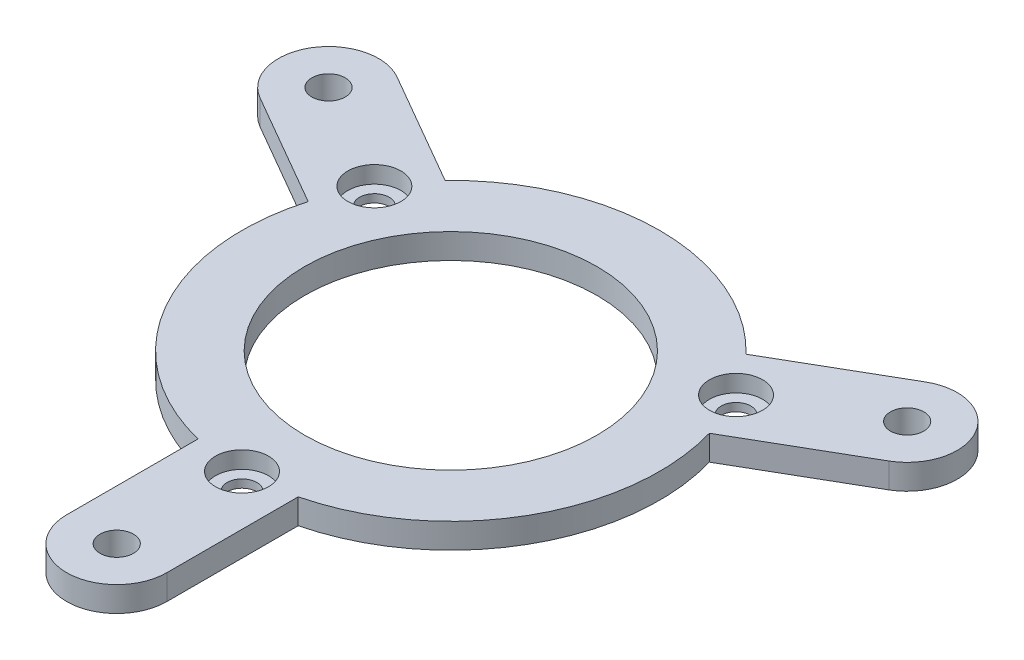
SolidWorks part; units mm, degrees
material "Delrin 2700 NC010, Low Viscosity Acetal Copolymer (SS)"
ref_plane "Front" through (0, 0, 0) normal (0, 0, 1) x (1, 0, 0)
ref_plane "Top" through (0, 0, 0) normal (0, 1, 0) x (1, 0, 0)
ref_plane "Right" through (0, 0, 0) normal (1, 0, 0) x (0, 0, -1)
sketch "Sketch1" plane through (0, 0, 0) normal (0, 1, 0) x (1, 0, 0)
  line L0 (0, 0) -> (-17.3205, 10) construction
  line L5 (0, 0) -> (0, -20) construction
  line L8 (3, 0) -> (3, -20)
  line L9 (-3, 0) -> (-3, -20)
  line L10 (-1.5, -2.5981) -> (-18.8205, 7.4019)
  line L11 (1.5, 2.5981) -> (-15.8205, 12.5981)
  line L12 (0, 0) -> (17.3205, 10) construction
  line L13 (-1.5, 2.5981) -> (15.8205, 12.5981)
  line L14 (1.5, -2.5981) -> (18.8205, 7.4019)
  circle A0 centre (0, 0) radius 17.5
  circle A1 centre (0, 0) radius 7.5
  arc A11 (3, 0) -> (-3, 0) centre (0, 0) ccw
  arc A12 (-3, -20) -> (3, -20) centre (0, -20) ccw
  circle A13 centre (0, -20) radius 1
  circle A14 centre (-17.3205, 10) radius 1
  arc A15 (-1.5, -2.5981) -> (1.5, 2.5981) centre (0, 0) ccw
  arc A16 (-15.8205, 12.5981) -> (-18.8205, 7.4019) centre (-17.3205, 10) ccw
  circle A17 centre (17.3205, 10) radius 1
  arc A18 (-1.5, 2.5981) -> (1.5, -2.5981) centre (0, 0) ccw
  arc A19 (18.8205, 7.4019) -> (15.8205, 12.5981) centre (17.3205, 10) ccw
  circle A20 centre (0, 0) radius 8.75
  circle A21 centre (0, 0) radius 12.5
  point P6 (-8.6603, 5)
  point P10 (0, -10)
  point P22 (8.6603, 5)
  point P30 (0, -23)
  dimension "D1" = 35
  dimension "D2" = 15
  dimension "D3" = 3
  dimension "D5" = 25
  dimension "D6" = 3
  dimension "D7" = 2
  dimension "D4" = 17.5
  dimension "D8" = 20
extrude "Boss-Extrude1" add sketch "Sketch1" along normal blind 1.5 contours L11 A16 L10 A0 A14 | A21 L11 A0 A14 L10 | L11 A21 L10 A20 | L10 A21 L9 A20 | L9 A21 L8 A20 | A21 L9 A0 A13 L8 | A13 A0 L9 A12 L8 | L8 A21 L14 A20 | L14 A21 L13 A20 | A21 L14 A0 A17 L13 | L14 A19 L13 A0 A17 | L13 A21 L11 A20 region at (8.4488, 0, 4.8779) region at (0, 0, 10.4755) region at (9.072, 0, -5.2377) region at (0, 0, 14.8958) region at (-8.4488, 0, 4.8779) region at (12.9002, 0, -7.4479) region at (0, 0, -9.7558) region at (-9.072, 0, -5.2377) region at (2.9168, 0, 18.6205) region at (15.2404, 0, -8.799) region at (-12.9002, 0, -7.4479) region at (-15.2404, 0, -8.799)
sketch "Sketch2" plane through (0, 1.5, 0) normal (0, 1, 0) x (1, 0, 0)
  line L0 (0, 0) -> (0, -12.5) construction
  line L1 (0, 0) -> (-10.8253, 6.25) construction
  line L2 (0, 0) -> (10.8253, 6.25) construction
  dimension "D1" = 12.5
  dimension "D2" = 3
hole_wizard "CBORE for #0 Socket Head Cap Screw1" positions "Sketch3" profile "Sketch4" counterbore size "#0" standard "ANSI Inch" end condition through all
sketch "Sketch3" plane through (0, 1.5, 0) normal (0, 1, 0) x (1, 0, 0)
  point P0 (-10.8253, 6.25)
  point P3 (10.8253, 6.25)
  point P6 (0, -12.5)
sketch "Sketch4" plane through (-10.8253, 1.5, -6.25) normal (1, 0, 0) x (0, 0, 1)
  line L0 (0, 0) -> (0, 1.5)
  line L1 (0, 1.5) -> (0.889, 1.5)
  line L3 (0.889, 1.5) -> (0.889, 1.016)
  line L4 (0.889, 1.016) -> (1.5875, 1.016)
  line L5 (1.5875, 1.016) -> (1.5875, 0)
  line L7 (1.5875, 0) -> (0, 0)
  line L11 (0, -6.35) -> (0, 107.95) construction
  dimension "Thru Hole Dia." = 1.778
  dimension "Thru Hole Depth" = 1.5
  dimension "C'Bore Dia." = 3.175
  dimension "C'Bore Depth" = 1.016
